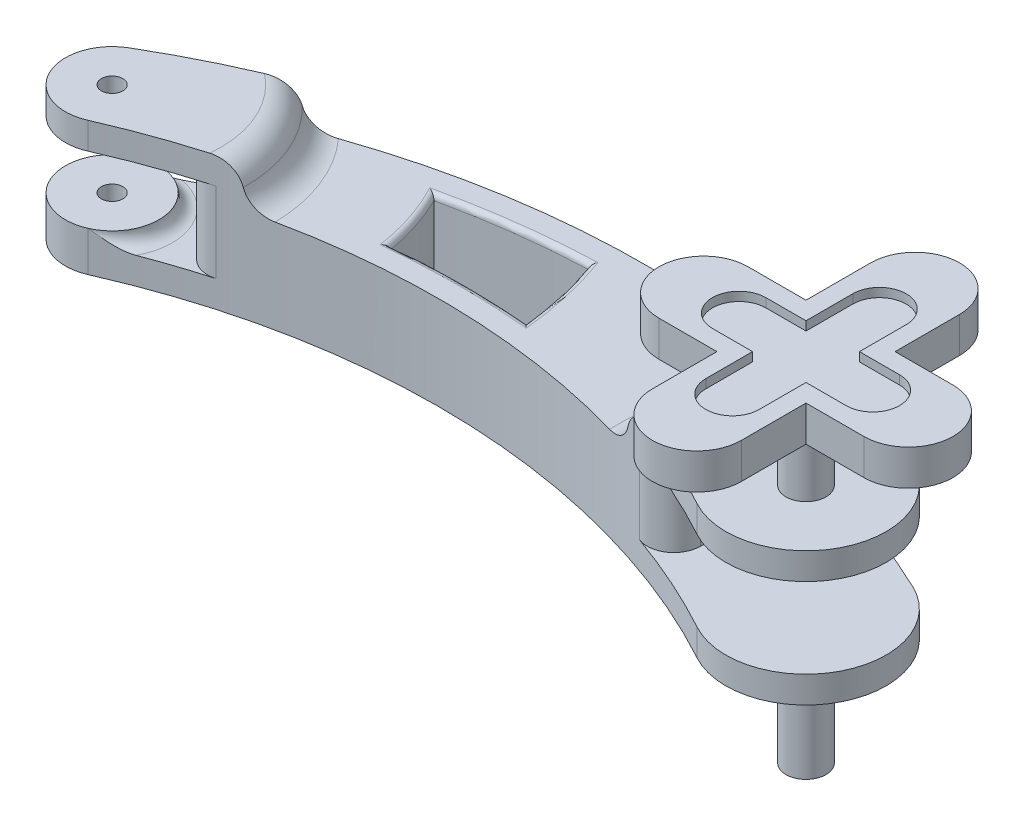
SolidWorks part; units mm, degrees
material "Dökme Alaşımlı Çelik"
ref_plane "Ön Düzlem" through (0, 0, 0) normal (0, 0, 1) x (1, 0, 0)
ref_plane "Üst Düzlem" through (0, 0, 0) normal (0, 1, 0) x (1, 0, 0)
ref_plane "Sağ Düzlem" through (0, 0, 0) normal (1, 0, 0) x (0, 0, -1)
sketch "Sketch1" plane through (0, 0, 0) normal (0, 1, 0) x (1, 0, 0)
  arc A0 (-8.8654, 15.0883) -> (7.0407, -16.0212) centre (0, 0) ccw
  arc A1 (245.2279, -26.3205) -> (272.5691, 27.0631) centre (259.6234, 0) ccw
  arc A2 (7.0407, -16.0212) -> (245.2279, -26.3205) centre (115.6686, -263.2053) cw
  arc A3 (-8.8654, 15.0883) -> (272.5691, 27.0631) centre (143.1122, -243.5675) cw
  circle A4 centre (0, 0) radius 4
  dimension "D1" = 35
  dimension "D2" = 60
  dimension "D3" = 259.6234
  dimension "D4" = 270
  dimension "D5" = 300
  dimension "D6" = 8
extrude "Boss-Extrude3" add sketch "Sketch1" along normal blind 50
ref_plane "Plane3" through (0, 25, 0) normal (0, 1, 0) x (1, 0, 0)
sketch "Sketch4" plane through (0, 25, 0) normal (0, 1, 0) x (1, 0, 0)
  line L4 (211.9733, -10.9645) -> (212.1066, -11.5382)
  circle A0 centre (0, 0) radius 30
  circle A1 centre (259.6234, 0) radius 40
  arc A5 (245.2279, -26.3205) -> (7.0407, -16.0212) centre (115.6686, -263.2053) ccw construction
extrude "Cut-Extrude3" cut sketch "Sketch4" against normal blind 15 and the other way blind 15 contours A1 | A0 region at (0, 25, 0) region at (259.6234, 25, 0)
sketch "Sketch5" plane through (0, 10, 0) normal (0, 1, 0) x (1, 0, 0)
  circle A0 centre (0, 0) radius 17.5
  circle A1 centre (0, 0) radius 4
  dimension "D1" = 35
  dimension "D2" = 8
extrude "Boss-Extrude5" add sketch "Sketch5" along normal blind 5
fillet "Fillet1" radius 5 1 edges at (15.5815, 10, -7.9667)
fillet "Fillet2" radius 10 4 edges at (246.8785, 25, -37.9153) (222.6706, 25, 15.313) (13.2979, 25, -26.8918) (29.0538, 25, 7.4752)
sketch "Sketch6" plane through (0, 50, 0) normal (0, 1, 0) x (1, 0, 0)
  arc A0 (0, -50) -> (0, 50) centre (0, 0) ccw
  arc A1 (259.6234, 60) -> (259.6234, -60) centre (259.6234, 0) ccw
  arc A2 (0, 50) -> (259.6234, 60) centre (147.8749, -413.9624) cw
  arc A4 (0, -50) -> (259.6234, -60) centre (146.4458, 376.8613) ccw
extrude "Cut-Extrude4" cut sketch "Sketch6" against normal blind 15
fillet "Fillet3" radius 10 2 edges at (203.9463, 35, -22.362) (46.2387, 35, -19.0258)
fillet "Fillet4" radius 10 2 edges at (46.2387, 50, -19.0258) (203.9463, 50, -22.362)
sketch "Sketch7" plane through (0, 35, 0) normal (0, 1, 0) x (1, 0, 0)
  arc A2 (88.6572, 15.4888) -> (80.7918, 39.6571) centre (0, 0) ccw
  arc A6 (139.1042, 15.8122) -> (132.1485, 46.2251) centre (0, 0) ccw
  arc A7 (139.733, 8.6417) -> (117.6834, 75.8328) centre (0, 0) ccw construction
  arc A10 (132.1485, 46.2251) -> (80.7918, 39.6571) centre (143.1122, -243.5675) ccw
  arc A12 (139.1042, 15.8122) -> (88.6572, 15.4888) centre (115.6686, -263.2053) ccw
  arc A17 (89.8284, 5.5554) -> (75.6536, 48.7497) centre (0, 0) ccw construction
  dimension "D3" = 290
  dimension "D4" = 90
  dimension "D1" = 279.0175
  dimension "D2" = 50
extrude "Cut-Extrude5" cut sketch "Sketch7" against normal through all
fillet "Fillet5" radius 2 8 edges at (85.5819, 0, -27.852) (106.3233, 0, -44.0895) (113.8734, 0, -16.789) (136.4762, 0, -31.213) (113.8734, 35, -16.789) (136.4762, 35, -31.213) (85.5819, 35, -27.852) (106.3233, 35, -44.0895)
sketch "Esquisse1" plane through (0, 50, 0) normal (0, 1, 0) x (1, 0, 0)
  circle A0 centre (259.6234, 0) radius 7.5
  arc A1 (245.2279, -26.3205) -> (272.5691, 27.0631) centre (259.6234, 0) ccw construction
  dimension "D1" = 15
extrude "Boss.-Extru.1" add sketch "Esquisse1" along normal blind 30
sketch "Esquisse2" plane through (0, 0, 0) normal (0, -1, 0) x (-1, 0, 0)
  circle A0 centre (-259.6234, 0) radius 7.5
  arc A1 (-272.5691, 27.0631) -> (-245.2279, -26.3205) centre (-259.6234, 0) ccw construction
  dimension "D1" = 15
extrude "Boss.-Extru.2" add sketch "Esquisse2" along normal blind 40
scale "Echelle1" bodies to scale 110 scale about centroid uniform scaling yes scale factor 0.6
sketch "Esquisse3" plane through (0, 56.2826, 0) normal (0, 1, 0) x (1, 0, 0)
  line L0 (215.3281, -16.9572) -> (215.3281, 32.0428) construction
  line L1 (205.3281, -16.9572) -> (205.3281, 32.0428)
  line L2 (225.3281, -16.9572) -> (225.3281, 32.0428)
  line L3 (192.3281, 7.5428) -> (238.3281, 7.5428) construction
  line L6 (192.3281, 17.5428) -> (238.3281, 17.5428)
  line L7 (192.3281, -2.4572) -> (238.3281, -2.4572)
  arc A0 (205.3281, -16.9572) -> (225.3281, -16.9572) centre (215.3281, -16.9572) ccw
  arc A1 (225.3281, 32.0428) -> (205.3281, 32.0428) centre (215.3281, 32.0428) ccw
  arc A4 (192.3281, 17.5428) -> (192.3281, -2.4572) centre (192.3281, 7.5428) ccw
  arc A5 (238.3281, -2.4572) -> (238.3281, 17.5428) centre (238.3281, 7.5428) ccw
  point P2 (215.3281, 7.5428)
  point P10 (215.3281, 7.5428)
  circle M3 centre (215.3281, 7.5428) radius 4.5
  dimension "D1" = 10
  dimension "D3" = 46
  dimension "D4" = 10
  dimension "D2" = 49
extrude "Boss.-Extru.3" add sketch "Esquisse3" along normal blind 8 contours L6 A4 L7 L1 | L2 A1 L1 L6 | L1 L7 L2 L6 M3 | M3 | L1 A0 L2 L7 | L7 A5 L6 L2 region at (215.3281, 56.2826, 13.7456) region at (194.7816, 56.2826, -7.5428) region at (205.6109, 56.2826, -7.5428) region at (215.3281, 56.2826, -28.8312) region at (235.8745, 56.2826, -7.5428) region at (215.3281, 56.2826, -7.5428)
sketch "Esquisse5" plane through (0, 64.2826, 0) normal (0, 1, 0) x (1, 0, 0)
  line L0 (215.3281, -8.9572) -> (215.3281, 24.0428) construction
  line L1 (209.3281, -8.9572) -> (209.3281, 24.0428)
  line L2 (221.3281, -8.9572) -> (221.3281, 24.0428)
  line L3 (200.3281, 7.5428) -> (230.3281, 7.5428) construction
  line L4 (200.3281, 13.5428) -> (230.3281, 13.5428)
  line L5 (200.3281, 1.5428) -> (230.3281, 1.5428)
  arc A0 (209.3281, -8.9572) -> (221.3281, -8.9572) centre (215.3281, -8.9572) ccw
  arc A1 (221.3281, 24.0428) -> (209.3281, 24.0428) centre (215.3281, 24.0428) ccw
  arc A2 (225.3281, 32.0428) -> (205.3281, 32.0428) centre (215.3281, 32.0428) ccw construction
  arc A3 (238.3281, -2.4572) -> (238.3281, 17.5428) centre (238.3281, 7.5428) ccw construction
  arc A4 (200.3281, 13.5428) -> (200.3281, 1.5428) centre (200.3281, 7.5428) ccw
  arc A5 (230.3281, 1.5428) -> (230.3281, 13.5428) centre (230.3281, 7.5428) ccw
  point P2 (215.3281, 7.5428)
  point P15 (215.3281, 7.5428)
  dimension "D3" = 6
  dimension "D6" = 6
  dimension "D1" = 24.5
  dimension "D2" = 33
  dimension "D4" = 23
  dimension "D5" = 30
extrude "Enlèv. mat.-Extru.1" cut sketch "Esquisse5" against normal blind 2 contours L4 A4 L5 L1 | L2 A1 L1 L4 | L1 L5 L2 L4 | L5 A5 L4 L2 | L1 A0 L2 L5 region at (215.3281, 64.2826, 6.1224) region at (202.4065, 64.2826, -7.5428) region at (215.3281, 64.2826, -7.5428) region at (215.3281, 64.2826, -21.2079) region at (228.2496, 64.2826, -7.5428)
